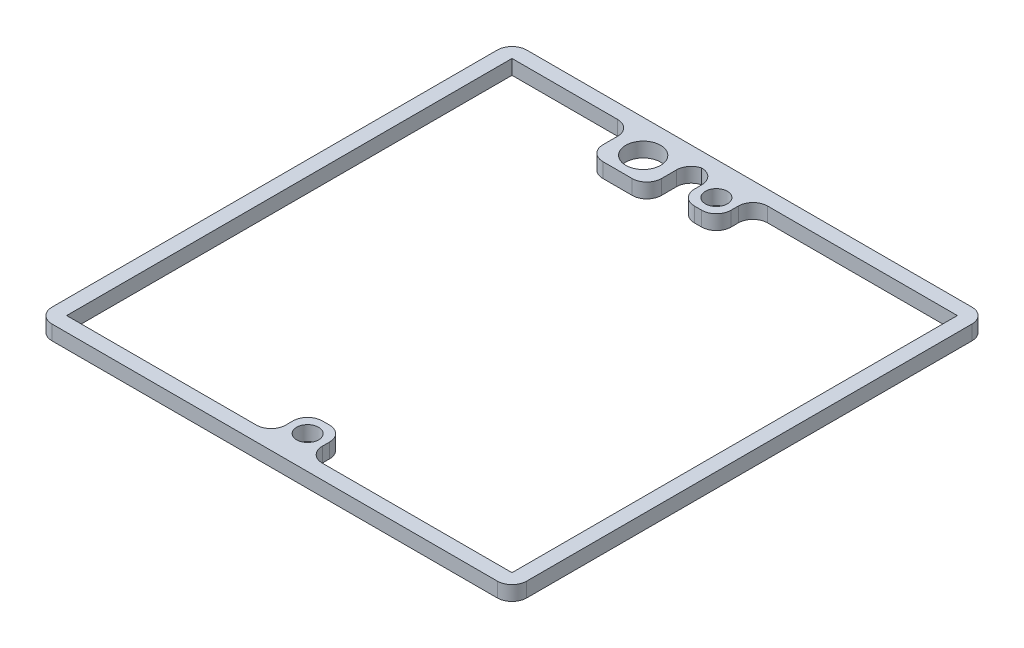
SolidWorks part; units mm, degrees
ref_plane "Front Plane" through (0, 0, 0) normal (0, 0, 1) x (1, 0, 0)
ref_plane "Top Plane" through (0, 0, 0) normal (0, 1, 0) x (1, 0, 0)
ref_plane "Right Plane" through (0, 0, 0) normal (1, 0, 0) x (0, 0, -1)
sketch "Sketch1" plane through (0, 0, 0) normal (0, 1, 0) x (1, 0, 0)
  line L0 (30.425, -30.425) -> (30.425, 30.425)
  line L1 (32.425, -32.425) -> (-32.425, -32.425)
  line L2 (32.425, -32.425) -> (32.425, 32.425)
  line L3 (32.425, 32.425) -> (-32.425, 32.425)
  line L4 (-32.425, -32.425) -> (-32.425, 32.425)
  line L5 (32.425, -32.425) -> (-32.425, 32.425) construction
  line L6 (32.425, 32.425) -> (-32.425, -32.425) construction
  line L7 (30.425, 30.425) -> (-30.425, 30.425)
  line L8 (-30.425, -30.425) -> (-30.425, 30.425)
  line L9 (30.425, -30.425) -> (-30.425, -30.425)
  point P0 (0, 0)
  dimension "D2" = 64.85
  dimension "D3" = 2
extrude "Boss-Extrude1" add sketch "Sketch1" along normal blind 2
sketch "Sketch2" plane through (0, 2, 0) normal (0, 1, 0) x (1, 0, 0)
  line L0 (30.425, 30.425) -> (-30.425, 30.425) construction
  line L1 (30.425, 30.425) -> (-30.425, 30.425)
  line L2 (0, 30.425) -> (0, -30.425) construction
  line L3 (-2.5, 30.425) -> (2.5, 30.425)
  line L4 (32.425, -32.425) -> (32.425, 32.425)
  line L5 (32.425, 32.425) -> (-32.425, 32.425)
  line L6 (-32.425, 32.425) -> (-32.425, -32.425)
  line L7 (-32.425, -32.425) -> (32.425, -32.425)
  line L8 (32.425, -32.425) -> (32.425, 32.425)
  line L9 (32.425, 32.425) -> (-32.425, 32.425)
  line L10 (-32.425, 32.425) -> (-32.425, -32.425)
  line L11 (-32.425, -32.425) -> (32.425, -32.425)
  line L12 (-2.5, 30.425) -> (-2.5, 25.425)
  line L13 (-2.5, 25.425) -> (2.5, 25.425)
  line L14 (2.5, 30.425) -> (2.5, 25.425)
  line L15 (-30.425, -30.425) -> (30.425, -30.425) construction
  line L16 (-30.425, 0) -> (30.425, 0) construction
  line L17 (-30.425, 30.425) -> (-30.425, -30.425) construction
  line L18 (30.425, -30.425) -> (30.425, 30.425) construction
  line L19 (2.5, -30.425) -> (2.5, -25.425)
  line L20 (-2.5, -30.425) -> (2.5, -30.425)
  line L21 (-2.5, -30.425) -> (-2.5, -25.425)
  line L22 (-2.5, -25.425) -> (2.5, -25.425)
  circle A0 centre (0, 27.925) radius 1.5
  circle A1 centre (0, -27.925) radius 1.5
  point P20 (0, 25.425)
  point P34 (-2.5, 27.925)
  line M29 (30.425, -30.425) -> (-30.425, -30.425)
  dimension "D4" = 3
  dimension "D3" = 5
extrude "Boss-Extrude2" add sketch "Sketch2" against normal up to surface (2 mm away) contours L14 L1 L12 L13 A0 | L22 L21 L19 A1 M29
fillet "Fillet1" radius 2
sketch "Sketch3" plane through (0, 2, 0) normal (0, 1, 0) x (1, 0, 0)
  line L0 (-4.5, 30.425) -> (-30.425, 30.425) construction
  line L1 (-14, 30.425) -> (-6, 30.425)
  line L2 (-14, 30.425) -> (-14, 24.425)
  line L3 (-14, 24.425) -> (-6, 24.425)
  line L4 (32.425, -30.425) -> (32.425, 30.425)
  line L5 (30.425, 32.425) -> (-30.425, 32.425)
  line L6 (-32.425, 30.425) -> (-32.425, -30.425)
  line L7 (-30.425, -32.425) -> (30.425, -32.425)
  line L8 (32.425, -30.425) -> (32.425, 30.425)
  line L9 (30.425, 32.425) -> (-30.425, 32.425)
  line L10 (-32.425, 30.425) -> (-32.425, -30.425)
  line L11 (-30.425, -32.425) -> (30.425, -32.425)
  line L12 (-6, 30.425) -> (-6, 24.425)
  circle A0 centre (0, 27.925) radius 1.5 construction
  circle A1 centre (0, 27.925) radius 1.5
  circle A2 centre (-10, 27.925) radius 2.3813
  arc A4 (32.425, 30.425) -> (30.425, 32.425) centre (30.425, 30.425) ccw
  arc A5 (-30.425, 32.425) -> (-32.425, 30.425) centre (-30.425, 30.425) ccw
  arc A6 (-32.425, -30.425) -> (-30.425, -32.425) centre (-30.425, -30.425) ccw
  arc A7 (30.425, -32.425) -> (32.425, -30.425) centre (30.425, -30.425) ccw
  arc A8 (32.425, 30.425) -> (30.425, 32.425) centre (30.425, 30.425) ccw
  arc A9 (-30.425, 32.425) -> (-32.425, 30.425) centre (-30.425, 30.425) ccw
  arc A10 (-32.425, -30.425) -> (-30.425, -32.425) centre (-30.425, -30.425) ccw
  arc A11 (30.425, -32.425) -> (32.425, -30.425) centre (30.425, -30.425) ccw
  point P23 (-10, 30.425)
  line M29 (-30.425, 30.425) -> (-4.5, 30.425)
  dimension "D2" = 4.7625
  dimension "D3" = 8
  dimension "D4" = 6
  dimension "D5" = 10
extrude "Boss-Extrude3" add sketch "Sketch3" against normal up to surface (2 mm away) contours L12 L2 L3 A2 M29
fillet "Fillet2" radius 2 4 edges at (-14, 1, -30.425) (-6, 1, -30.425) (-6, 1, -24.425) (-14, 1, -24.425)
equation "\"D\"= 65"
equation "\"D2@Sketch1\"=\"D\"-\"C\""
equation "\"T\"=2"
equation "\"D3@Sketch1\"=\"T\""
equation "\"D1@Boss-Extrude1\"=\"T\""
equation "\"F\"=2"
equation "\"D1@Fillet1\"=\"F\""
equation "\"TAB\"=5"
equation "\"D2@Sketch2\"=\"TAB\""
equation "\"D3@Sketch2\"=\"TAB\""
equation "\"TABH\"=3"
equation "\"D4@Sketch2\"=\"TABH\""
equation "\"C\"= 0.15"
equation "\"OUTPUTTUBE\"=4.7625"
equation "\"D2@Sketch3\"=\"OUTPUTTUBE\""
equation "\"OUTPUTL\"= 8"
equation "\"D3@Sketch3\"=\"OUTPUTL\""
equation "\"OUTPUTW\"= 6"
equation "\"D4@Sketch3\"=\"OUTPUTW\""
equation "\"D1@Fillet2\"=\"F\""
